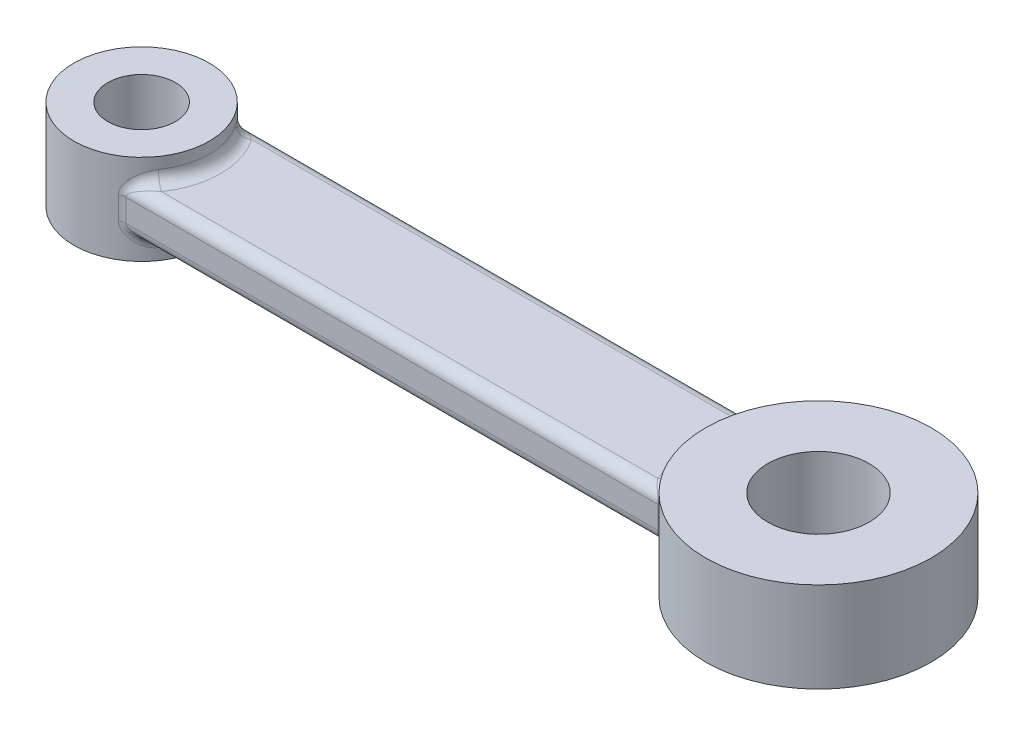
SolidWorks part; units mm, degrees
ref_plane "Front Plane" through (0, 0, 0) normal (0, 0, 1) x (1, 0, 0)
ref_plane "Top Plane" through (0, 0, 0) normal (0, 1, 0) x (1, 0, 0)
ref_plane "Right Plane" through (0, 0, 0) normal (1, 0, 0) x (0, 0, -1)
sketch "Sketch1" plane through (0, 0, 0) normal (0, 1, 0) x (1, 0, 0)
  line L1 (-15, -2.5) -> (15, -2.5)
  line L2 (-15, -2.5) -> (-15, 2.5)
  line L3 (-15, 2.5) -> (15, 2.5)
  line L4 (15, -2.5) -> (15, 2.5)
  line L5 (-15, -2.5) -> (15, 2.5) construction
  line L6 (-15, 2.5) -> (15, -2.5) construction
  point P0 (0, 0)
  dimension "D1" = 30
  dimension "D2" = 5
extrude "Boss-Extrude1" add sketch "Sketch1" along normal mid plane 2
sketch "Sketch2" plane through (0, 0, 0) normal (0, 1, 0) x (1, 0, 0)
  line L0 (15, -2.5) -> (15, 2.5) construction
  line L1 (-15, 2.5) -> (-15, -2.5) construction
  circle A0 centre (15, 0) radius 5
  circle A1 centre (-15, 0) radius 3
  dimension "D1" = 6
  dimension "D2" = 10
extrude "Boss-Extrude2" add sketch "Sketch2" along normal mid plane 4
sketch "Sketch3" plane through (0, 2, 0) normal (0, 1, 0) x (1, 0, 0)
  circle A1 centre (-15, 0) radius 1.5
  circle A2 centre (15, 0) radius 2.25
  dimension "D1" = 3
  dimension "D2" = 4.5
extrude "Cut-Extrude1" cut sketch "Sketch3" against normal through all
fillet "Fillet1" radius 0.5 4 edges at (-1.3359, -1, -2.5) (-1.3359, 1, -2.5) (-1.3359, -1, 2.5) (-1.3359, 1, 2.5)
fillet "Fillet2" radius 0.5 16 edges at (-13.2762, 0.7066, 2.4553) (-13.3417, 0, 2.5) (-13.1981, -0.8019, 2.3986) (-12, -1, 0) (-13.2762, -0.7066, -2.4553) (-13.3417, 0, -2.5) (-13.1981, 0.8019, -2.3986) (10.6204, 0.7829, -2.4123) (10.6699, 0, -2.5) (10.5801, -0.8688, -2.3376) (10, -1, 0) (10.6204, -0.7829, 2.4123) (10.6699, 0, 2.5) (10.5801, 0.8688, 2.3376) (-12, 1, 0) (10, 1, 0)
